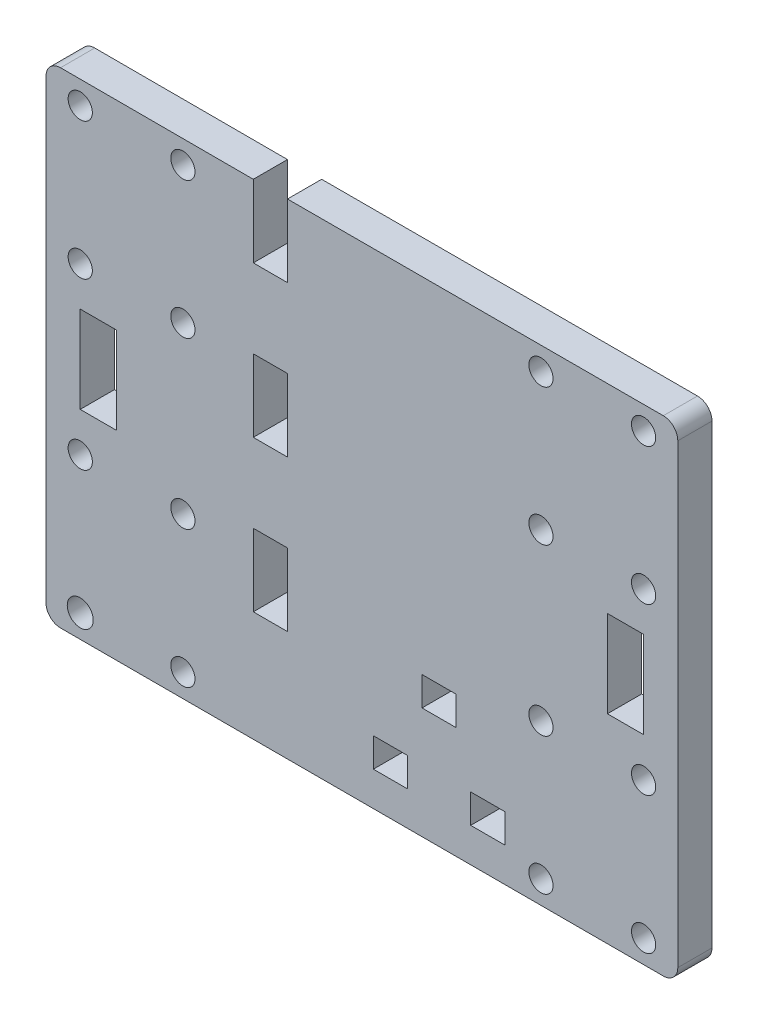
SolidWorks part; units mm, degrees
ref_plane "Front Plane" through (0, 0, 0) normal (0, 0, 1) x (1, 0, 0)
ref_plane "Top Plane" through (0, 0, 0) normal (0, 1, 0) x (1, 0, 0)
ref_plane "Right Plane" through (0, 0, 0) normal (1, 0, 0) x (0, 0, -1)
sketch "Sketch1" plane through (0, 0, 0) normal (0, 0, 1) x (1, 0, 0)
  line L0 (333.6594, 144.0694) -> (339.6538, 144.0694)
  line L1 (375.975, 144.0694) -> (270.255, 144.0694)
  line L2 (378.515, 146.6094) -> (378.515, 226.6327)
  line L3 (270.258, 229.1713) -> (304.065, 229.1314)
  line L4 (267.715, 146.6094) -> (267.715, 226.6313)
  line L5 (310.0594, 229.1314) -> (375.9734, 229.1727)
  line L6 (339.6538, 163.6283) -> (333.6594, 163.6283)
  line L7 (339.6538, 163.6283) -> (339.6538, 168.7083)
  line L8 (331.1194, 155.1438) -> (331.1194, 150.0638)
  line L9 (331.1194, 150.0638) -> (325.125, 150.0638)
  line L10 (325.125, 150.0638) -> (325.125, 155.1438)
  line L11 (325.125, 155.1438) -> (331.1194, 155.1438)
  line L12 (339.6538, 168.7083) -> (333.6594, 168.7083)
  line L13 (348.1882, 155.1438) -> (342.1938, 155.1438)
  line L14 (348.1882, 150.0638) -> (348.1882, 155.1438)
  line L15 (342.1938, 150.0638) -> (348.1882, 150.0638)
  line L16 (342.1938, 155.1438) -> (342.1938, 150.0638)
  line L17 (333.6594, 163.6283) -> (333.6594, 168.7083)
  line L18 (310.0594, 163.4314) -> (304.065, 163.4314)
  line L19 (310.0594, 163.4314) -> (310.0594, 176.1314)
  line L20 (310.0594, 176.1314) -> (304.065, 176.1314)
  line L21 (304.065, 163.4314) -> (304.065, 176.1314)
  line L22 (304.065, 189.9314) -> (310.0594, 189.9314)
  line L23 (304.065, 189.9314) -> (304.065, 202.6314)
  line L24 (304.065, 202.6314) -> (310.0594, 202.6314)
  line L25 (310.0594, 189.9314) -> (310.0594, 202.6314)
  line L26 (310.0594, 216.4314) -> (304.065, 216.4314)
  line L27 (310.0594, 216.4314) -> (310.0594, 229.1314)
  line L29 (304.065, 216.4314) -> (304.065, 229.1314)
  line L30 (378.515, 226.6327) -> (384.5094, 226.6327)
  line L31 (384.5094, 226.6327) -> (444.9261, 226.6327)
  line L32 (384.5094, 226.6327) -> (384.5094, 144.0694)
  line L33 (384.5094, 144.0694) -> (444.9261, 144.0694)
  line L34 (444.9261, 226.6327) -> (444.9261, 144.0694)
  line L35 (273.7094, 186.6203) -> (273.7094, 194.2403)
  line L36 (273.7094, 194.2403) -> (280.0594, 194.2403)
  line L37 (280.0594, 194.2403) -> (280.0594, 179.0003)
  line L38 (280.0594, 179.0003) -> (273.7094, 179.0003)
  line L39 (273.7094, 179.0003) -> (273.7094, 186.6203)
  line L40 (372.5206, 179.0003) -> (372.5206, 186.6203)
  line L41 (366.1706, 179.0003) -> (372.5206, 179.0003)
  line L42 (366.1706, 194.2403) -> (366.1706, 179.0003)
  line L43 (372.5206, 194.2403) -> (366.1706, 194.2403)
  line L44 (372.5206, 186.6203) -> (372.5206, 194.2403)
  circle A0 centre (372.515, 148.1123) radius 2.125
  circle A1 centre (354.515, 148.1123) radius 2.125
  circle A2 centre (372.515, 172.1123) radius 2.125
  circle A3 centre (354.515, 172.1123) radius 2.125
  circle A4 centre (291.715, 148.1123) radius 2.125
  circle A5 centre (273.715, 148.1123) radius 2.2816
  circle A6 centre (291.715, 172.1123) radius 2.125
  circle A7 centre (273.715, 172.1123) radius 2.125
  circle A8 centre (372.515, 201.1314) radius 2.125
  circle A9 centre (354.515, 201.1314) radius 2.125
  circle A10 centre (372.515, 225.1314) radius 2.125
  circle A11 centre (354.515, 225.1314) radius 2.125
  circle A12 centre (291.715, 201.1314) radius 2.125
  circle A13 centre (273.715, 201.1314) radius 2.125
  circle A14 centre (291.715, 225.1314) radius 2.125
  circle A15 centre (273.715, 225.1314) radius 2.125
  arc A16 (378.515, 226.6327) -> (375.9734, 229.1727) centre (375.975, 226.6327) ccw
  arc A17 (270.258, 229.1713) -> (267.715, 226.6313) centre (270.255, 226.6313) ccw
  arc A18 (270.255, 144.0694) -> (267.715, 146.6094) centre (270.255, 146.6094) cw
  arc A19 (375.975, 144.0694) -> (378.515, 146.6094) centre (375.975, 146.6094) ccw
  point P68 (331.1194, 152.6038)
  dimension "D1" = 2.54
  dimension "D2" = 2.54
  dimension "D3" = 2.54
  dimension "D4" = 2.54
extrude "Boss-Extrude1" add sketch "Sketch1" along normal blind 5.9944
